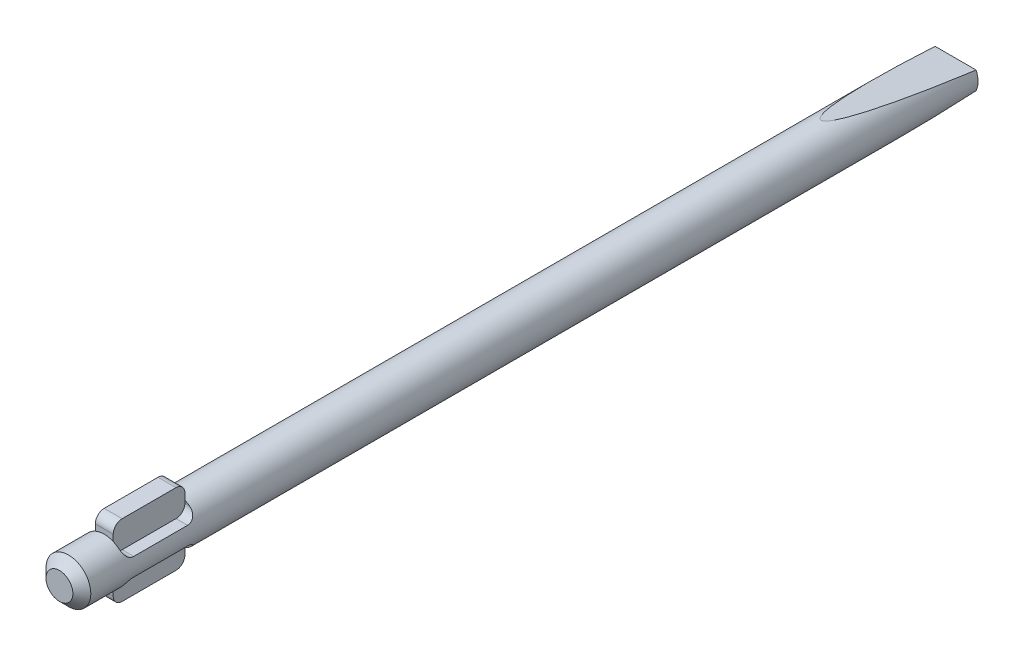
SolidWorks part; units mm, degrees
ref_plane "Front Plane" through (0, 0, 0) normal (0, 0, 1) x (1, 0, 0)
ref_plane "Top Plane" through (0, 0, 0) normal (0, 1, 0) x (1, 0, 0)
ref_plane "Right Plane" through (0, 0, 0) normal (1, 0, 0) x (0, 0, -1)
sketch "Sketch1" plane through (0, 0, 0) normal (0, 0, 1) x (1, 0, 0)
  circle A0 centre (0, 0) radius 2.5
  dimension "D1" = 5
extrude "Boss-Extrude1" add sketch "Sketch1" along normal blind 100
sketch "Sketch2" plane through (0, 0, 0) normal (1, 0, 0) x (0, 0, -1)
  line L0 (-100, 2.5) -> (-100, -2.5) construction
  line L1 (-94, 4) -> (-88, 4)
  line L2 (-95, 3) -> (-95, 2)
  line L3 (-94, 1) -> (-88, 1)
  line L4 (-87, 3) -> (-87, 2)
  line L5 (-100, 0) -> (-80.9978, 0) construction
  line L6 (-87, -3) -> (-87, -2)
  line L7 (-94, -1) -> (-88, -1)
  line L8 (-95, -3) -> (-95, -2)
  line L9 (-94, -4) -> (-88, -4)
  arc A0 (-88, 1) -> (-87, 2) centre (-88, 2) ccw
  arc A1 (-95, 2) -> (-94, 1) centre (-94, 2) ccw
  arc A2 (-94, 4) -> (-95, 3) centre (-94, 3) ccw
  arc A3 (-88, 4) -> (-87, 3) centre (-88, 3) cw
  arc A4 (-88, -4) -> (-87, -3) centre (-88, -3) ccw
  arc A5 (-88, -1) -> (-87, -2) centre (-88, -2) cw
  arc A6 (-95, -2) -> (-94, -1) centre (-94, -2) cw
  arc A7 (-94, -4) -> (-95, -3) centre (-94, -3) cw
  point P11 (-87, 1)
  point P14 (-95, 1)
  point P19 (-87, 4)
  dimension "D5" = 1
  dimension "D1" = 3
  dimension "D2" = 8
  dimension "D3" = 5
  dimension "D4" = 1
extrude "Cut-Extrude1" cut sketch "Sketch2" against normal mid plane 10
extrude "Boss-Extrude2" add sketch "Sketch2<2>" along normal mid plane 2
sketch "Sketch2<2>" plane through (0, 0, 0) normal (1, 0, 0) x (0, 0, -1) same geometry as "Sketch2"
sketch "Sketch3" plane through (0, 0, 100) normal (0, 0, 1) x (1, 0, 0)
sketch "Sketch4" plane through (0, 0, 0) normal (1, 0, 0) x (0, 0, -1)
  line L0 (0, 1) -> (0, -1)
  line L1 (0, -2.5) -> (0, 2.5) construction
  line L2 (0, -1) -> (-15, -2.5)
  line L3 (-87, -2.5) -> (0, -2.5) construction
  line L5 (0, 2.5) -> (-87, 2.5) construction
  line L6 (-15, 2.5) -> (0, 1)
  line L7 (-15, -2.5) -> (0, -2.5)
  line L8 (0, -2.5) -> (0, 2.5)
  line L9 (0, 2.5) -> (-15, 2.5)
  point P6 (0, 0)
  dimension "D1" = 2
  dimension "D2" = 15
  dimension "D3" = 15
extrude "Cut-Extrude2" cut sketch "Sketch4" against normal mid plane 12 contours L8 L9 L6 | L7 L8 L2 region at (0, -2, 5) region at (0, 2, 5)
chamfer "Chamfer1" distance 1 angle 45 1 edges at (2.5, 0, 100)
